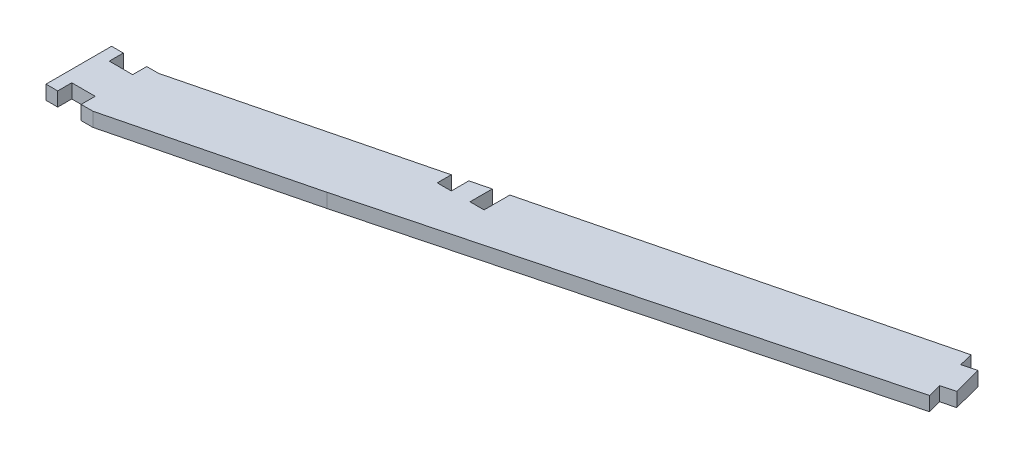
SolidWorks part; units mm, degrees
ref_plane "Front Plane" through (0, 0, 0) normal (0, 0, 1) x (1, 0, 0)
ref_plane "Top Plane" through (0, 0, 0) normal (0, 1, 0) x (1, 0, 0)
ref_plane "Right Plane" through (0, 0, 0) normal (1, 0, 0) x (0, 0, -1)
sketch "Sketch1" plane through (0, 0, 0) normal (0, 1, 0) x (1, 0, 0)
  line L0 (-450, 300) -> (-400, 300)
  line L1 (-400, 300) -> (-200, 250)
  line L2 (-200, 250) -> (200, 250) construction
  line L3 (200, 250) -> (600, 40) construction
  line L4 (600, 40) -> (1200, 40)
  line L5 (-450, -300) -> (-400, -300)
  line L6 (-400, -300) -> (-200, -250)
  line L7 (-200, -250) -> (200, -250) construction
  line L8 (200, -250) -> (600, -40) construction
  line L9 (600, -40) -> (1200, -40)
  line L10 (600, 40) -> (600, -40) construction
  line L11 (200, -250) -> (200, 250) construction
  line L12 (-200, 250) -> (-200, -250) construction
  line L13 (-400, -300) -> (-400, 300) construction
  line L14 (0, 0) -> (200, 0) construction
  line L15 (0, 250) -> (0, 0) construction
  line L16 (1200, 40) -> (1200, -40)
  line L17 (-450, 300) -> (-450, -300)
  line L18 (600, 0) -> (200, 0) construction
  line L19 (-450, 0) -> (-400, 0) construction
  line L20 (-400, 0) -> (-200, 0) construction
  line L21 (-200, 0) -> (0, 0) construction
  line L22 (-200, 250) -> (600, 40)
  line L23 (600, -40) -> (-200, -250)
  dimension "D1" = 600
  dimension "D2" = 200
  dimension "D3" = 50
  dimension "D4" = 400
  dimension "D5" = 500
  dimension "D6" = 80
  dimension "D7" = 600
  dimension "D8" = 400
extrude "Boss-Extrude1" add sketch "Sketch1" along normal blind 15
sketch "Sketch2" plane through (0, 0, 0) normal (0, 0, 1) x (1, 0, 0)
  line L0 (-450, 0) -> (-450, -40)
  line L1 (-450, -40) -> (-400, -40)
  line L2 (-400, -40) -> (-400, 0)
  line L3 (-400, 0) -> (-200, 0) construction
  line L4 (-400, 0) -> (-450, 0)
  line L5 (-440, -15) -> (-440, -40)
  line L6 (-410, -15) -> (-410, -40)
  line L7 (-425, 0) -> (-425, -15) construction
  circle A0 centre (-425, -15) radius 15
  dimension "D1" = 30
  dimension "D2" = 40
extrude "Boss-Extrude2" add sketch "Sketch2" along normal up to surface and the other way up to surface contours L4 L7 A0 L6 L1 L2 | L7 L4 L0 L1 L5 A0 up to face at (-425, 7.5, 300) other way up to face at (-425, 7.5, -300)
sketch "Sketch4" plane through (0, 0, 0) normal (0, 1, 0) x (1, 0, 0)
  line L0 (-450, 230) -> (-400, 230)
  line L1 (-450, 300) -> (-450, -300) construction
  line L2 (-400, 230) -> (-150, 167.5)
  line L3 (-150, 167.5) -> (-150, -167.5)
  line L4 (-150, -167.5) -> (-400, -230)
  line L5 (-400, -230) -> (-450, -230)
  line L6 (-400, 230) -> (-400, -230) construction
  line L7 (-200, 250) -> (-200, -250) construction
  line L9 (-200, 0) -> (-150, 0) construction
  line L10 (-400, -230) -> (-400, -300) construction
  line L11 (-400, -300) -> (-200, -250) construction
  line L12 (-450, 230) -> (-450, -230)
  line L14 (-200, 250) -> (-400, 300) construction
  line L15 (-100, 155) -> (-100, -155)
  line L16 (-100, -155) -> (520, 0)
  line L17 (520, 0) -> (-100, 155)
  line L18 (520, 0) -> (-100, 0) construction
  dimension "D1" = 460
  dimension "D2" = 300
  dimension "D3" = 50
extrude "Cut-Extrude2" cut sketch "Sketch4" against normal through all both and the other way through all
sketch "Sketch5" plane through (0, 0, 0) normal (1, 0, 0) x (0, 0, -1)
  line L0 (-300, 0) -> (-230, 0) construction
  line L1 (-285, 0) -> (-245, 0)
  line L2 (-285, 0) -> (-285, -40)
  line L3 (-285, -40) -> (-245, -40)
  line L4 (-245, 0) -> (-245, -40)
  line L5 (-300, -40) -> (-230, -40) construction
  line L6 (230, 0) -> (300, 0) construction
  line L7 (245, 0) -> (285, 0)
  line L8 (245, 0) -> (245, -40)
  line L9 (245, -40) -> (285, -40)
  line L10 (285, 0) -> (285, -40)
  line L11 (230, -40) -> (300, -40) construction
  line L12 (-300, 0) -> (-300, -40) construction
  line L13 (230, -40) -> (230, 0) construction
  line L14 (300, 0) -> (300, -40) construction
  dimension "D1" = 15
  dimension "D2" = 15
  dimension "D3" = 15
  dimension "D4" = 15
extrude "Cut-Extrude3" cut sketch "Sketch5" against normal through all
sketch "Sketch7" plane through (1200, 0, 0) normal (1, 0, 0) x (0, 0, -1)
  line L1 (-40, 15) -> (-87.5, 50)
  line L2 (-87.5, 50) -> (-87.5, 88.7)
  line L3 (-87.5, 88.7) -> (87.5, 88.7)
  line L4 (87.5, 88.7) -> (87.5, 50)
  line L5 (87.5, 50) -> (40, 15)
  line L7 (-40, 15) -> (40, 15)
  line L8 (-20, 50) -> (-20, 88.7)
  line L9 (87.5, 50) -> (-87.5, 50) construction
  line L10 (0, 88.7) -> (0, 50) construction
  line L11 (-20, 88.7) -> (20, 88.7)
  line L12 (0, 50) -> (0, 0) construction
  line L13 (20, 88.7) -> (20, 50)
  line L14 (-73, 88.7) -> (-63, 88.7)
  line L15 (-73, 88.7) -> (-73, 63.2)
  line L16 (-73, 63.2) -> (-63, 63.2)
  line L17 (-63, 88.7) -> (-63, 63.2)
  line L18 (48.5, 88.7) -> (58.5, 88.7)
  line L19 (48.5, 88.7) -> (48.5, 63.2)
  line L20 (48.5, 63.2) -> (58.5, 63.2)
  line L21 (58.5, 88.7) -> (58.5, 63.2)
  circle A0 centre (0, 50) radius 20
  dimension "D3" = 40
  dimension "D1" = 175
  dimension "D2" = 50
  dimension "D4" = 25.5
  dimension "D5" = 10
  dimension "D6" = 63
  dimension "D7" = 48.5
  dimension "D8" = 38.7
extrude "Boss-Extrude4" add sketch "Sketch7" against normal blind 75
sketch "Sketch8" plane through (0, 0, 0) normal (0, 0, 1) x (1, 0, 0)
  line L0 (1125, 88.7) -> (1200, 88.7) construction
  line L1 (1140, 88.7) -> (1185, 88.7)
  line L2 (1140, 88.7) -> (1140, 15)
  line L3 (1140, 15) -> (1185, 15)
  line L4 (1185, 88.7) -> (1185, 15)
  line L5 (1125, 15) -> (1200, 15) construction
  line L6 (1125, 50) -> (1125, 88.7) construction
  line L7 (1200, 50) -> (1200, 88.7) construction
  line L8 (1155, 88.7) -> (1170, 88.7) construction
  line L9 (1155, 88.7) -> (1170, 88.7)
  line L10 (1155, 88.7) -> (1155, 15)
  line L11 (1155, 15) -> (1170, 15)
  line L12 (1170, 88.7) -> (1170, 15)
  line L15 (1162.5, 50) -> (1162.5, 88.7) construction
  line L16 (1125, 50) -> (1200, 50) construction
  line L17 (1155, 88.7) -> (1170, 88.7) construction
  dimension "D1" = 15
  dimension "D2" = 15
  dimension "D3" = 15
extrude "Cut-Extrude4" cut sketch "Sketch8" against normal through all both and the other way through all contours L10 L1 L2 L3 | L1 L12 L3 L4
fillet "Fillet1" radius 5 53 edges at (1192.5, 50, 87.5) (1162.5, 50, 87.5) (1132.5, 50, 87.5) (1192.5, 50, -87.5) (1162.5, 50, -87.5) (1132.5, 50, -87.5) (1192.5, 88.7, -87.5) (1162.5, 88.7, -87.5) (1132.5, 88.7, -87.5) (1132.5, 88.7, -58.5) (1162.5, 88.7, -58.5) (1192.5, 88.7, -58.5) (1192.5, 88.7, -48.5) (1162.5, 88.7, -48.5) (1132.5, 88.7, -48.5) (1192.5, 88.7, -20) (1162.5, 88.7, -20) (1132.5, 88.7, -20) (1192.5, 88.7, 63) (1162.5, 88.7, 63) (1132.5, 88.7, 63) (1132.5, 88.7, 87.5) (1162.5, 88.7, 87.5) (1192.5, 88.7, 87.5) (1192.5, 88.7, 73) (1162.5, 88.7, 73) (1132.5, 88.7, 73) (1192.5, 88.7, 20) (1162.5, 88.7, 20) (1132.5, 88.7, 20) (600, 7.5, 40) (600, 7.5, -40) (520, 7.5, 0) (-440, -40, -292.5) (-440, -40, -237.5) (-400, -40, -292.5) (-400, -40, -237.5) (-450, -40, -237.5) (-410, -40, -237.5) (-450, -40, -292.5) (-410, -40, -292.5) (-150, 7.5, 167.5) (-100, 7.5, 155) (-150, 7.5, -167.5) (-100, 7.5, -155) (-450, -40, 237.5) (-410, -40, 237.5) (-440, -40, 237.5) (-400, -40, 237.5) (-450, -40, 292.5) (-440, -40, 292.5) (-400, -40, 292.5) (-410, -40, 292.5)
sketch "Sketch9" plane through (0, 0, 0) normal (0, 1, 0) x (1, 0, 0)
  line L35 (-450, -300) -> (-400, -300) construction
  line L36 (-425, -300) -> (-425, -285) construction
  line L37 (-450, 0) -> (0, 0) construction
  line L38 (-437.5, -300) -> (-412.5, -300)
  line L39 (-437.5, -300) -> (-437.5, -285)
  line L56 (1140, -40) -> (1140, -85.466) construction
  line L57 (1200, -40) -> (1185, -40)
  line L58 (1200, -40) -> (1200, -25)
  line L59 (1200, -25) -> (1185, -25)
  line L60 (1185, -40) -> (1185, -25)
  line L61 (1200, 40) -> (1185, 40)
  line L62 (1200, 40) -> (1200, 25)
  line L63 (1200, 25) -> (1185, 25)
  line L64 (1185, 40) -> (1185, 25)
  line L65 (1170, 40) -> (1155, 40)
  line L66 (1170, 40) -> (1170, 25)
  line L67 (1170, 25) -> (1155, 25)
  line L68 (1155, 40) -> (1155, 25)
  line L69 (1140, 40) -> (1125, 40)
  line L70 (1140, 40) -> (1140, 25)
  line L71 (1140, 25) -> (1125, 25)
  line L72 (1125, 40) -> (1125, 25)
  line L73 (1125, -40) -> (1140, -40)
  line L74 (1125, -40) -> (1125, -25)
  line L75 (1125, -25) -> (1140, -25)
  line L76 (1140, -40) -> (1140, -25)
  line L77 (1155, -40) -> (1170, -40)
  line L78 (1155, -40) -> (1155, -25)
  line L79 (1155, -25) -> (1170, -25)
  line L80 (1170, -40) -> (1170, -25)
  line L81 (600.6453, -40) -> (1200, -40) construction
  line L82 (1200, 40) -> (600.6453, 40) construction
  line L83 (1140, 40) -> (1125, 40) construction
  line L84 (1125, 85.466) -> (1125, 40) construction
  line L85 (1140, -25) -> (1155, -25) construction
  line L86 (1170, -25) -> (1185, -25) construction
  line L87 (1185, 25) -> (1170, 25) construction
  line L88 (1155, 25) -> (1140, 25) construction
  line L89 (-437.5, -285) -> (-412.5, -285)
  line L90 (-412.5, -300) -> (-412.5, -285)
  line L92 (-410, -230) -> (-440, -230) construction
  line L93 (-437.5, -230) -> (-412.5, -230)
  line L94 (-437.5, -230) -> (-437.5, -245)
  line L95 (-437.5, -245) -> (-412.5, -245)
  line L96 (-412.5, -230) -> (-412.5, -245)
  line L97 (-425, -245) -> (-400, -245) construction
  line L98 (-425, -285) -> (-425, -245) construction
  line L99 (-425, 285) -> (-425, 245) construction
  line L100 (-425, 300) -> (-425, 285) construction
  line L101 (-450, 300) -> (-400, 300) construction
  line L102 (-412.5, 230) -> (-412.5, 245)
  line L103 (-437.5, 245) -> (-412.5, 245)
  line L104 (-437.5, 230) -> (-437.5, 245)
  line L105 (-437.5, 230) -> (-412.5, 230)
  line L106 (-412.5, 300) -> (-412.5, 285)
  line L107 (-437.5, 285) -> (-412.5, 285)
  line L108 (-437.5, 300) -> (-437.5, 285)
  line L109 (-437.5, 300) -> (-412.5, 300)
  dimension "D1" = 15
  dimension "D2" = 25
  dimension "D3" = 15
extrude "Cut-Extrude5" cut sketch "Sketch9" against normal through all both and the other way through all
sketch "Sketch10" plane through (0, 0, 0) normal (0, 0, 1) x (1, 0, 0)
  line L1 (-450, 15) -> (1200, 15)
  line L2 (-450, 15) -> (-450, 0)
  line L3 (-450, 0) -> (1200, 0)
  line L4 (1200, 15) -> (1200, 0)
  line L5 (-450, 15) -> (-450, -35) construction
  line L6 (-486.0808, 110.0266) -> (1242.84, 110.0266)
  line L7 (-486.0808, 110.0266) -> (-486.0808, -68.8272)
  line L8 (-486.0808, -68.8272) -> (1242.84, -68.8272)
  line L9 (1242.84, 110.0266) -> (1242.84, -68.8272)
  dimension "D1" = 15
extrude "Cut-Extrude6" cut sketch "Sketch10" against normal through all both and the other way through all
sketch "Sketch11" plane through (0, 0, 0) normal (0, 1, 0) x (1, 0, 0)
  line L0 (-450, -315.625) -> (323.7848, -112.5065)
  line L1 (-200, -250) -> (599.3758, -40.1638) construction
  line L2 (-450, -315.625) -> (-450, -242.5)
  line L3 (-450, -230) -> (-450, -300) construction
  line L4 (-450, -242.5) -> (308.1542, -52.9615)
  line L5 (308.1542, -52.9615) -> (323.7848, -112.5065)
  line L6 (-400, -230) -> (-153.7873, -168.4468) construction
  line L7 (-450, -242.5) -> (-450, -230)
  line L8 (-450, -230) -> (-400, -230)
  line L9 (-150, -167.5) -> (-150, -182.5)
  line L10 (-150, -182.5) -> (-135, -182.5)
  line L11 (-135, -182.5) -> (-135, -163.75)
  line L12 (-100, -155) -> (-100, -182.5)
  line L13 (-100, -182.5) -> (-115, -182.5)
  line L14 (-115, -182.5) -> (-115, -158.75)
  line L15 (-100, 148.5961) -> (-100, -148.5961) construction
  line L16 (-150, -163.5961) -> (-150, 163.5961) construction
  line L17 (309.2763, -116.315) -> (305.4678, -101.8065)
  line L18 (-601.3695, -564.0724) -> (1251.3111, -564.0724)
  line L19 (-601.3695, -564.0724) -> (-601.3695, 511.8547)
  line L20 (-601.3695, 511.8547) -> (1251.3111, 511.8547)
  line L21 (1251.3111, -564.0724) -> (1251.3111, 511.8547)
  line L22 (305.4678, -101.8065) -> (319.9763, -97.998)
  line L23 (293.6011, -56.5997) -> (297.4095, -71.1082)
  line L24 (297.4095, -71.1082) -> (311.918, -67.2997)
  line L25 (305.4678, -101.8065) -> (297.4095, -71.1082) construction
  dimension "D1" = 800
  dimension "D2" = 15
  dimension "D3" = 15
  dimension "D4" = 15
  dimension "D5" = 15
extrude "Cut-Extrude9" cut sketch "Sketch11" against normal through all and the other way through all contours L18 L21 L20 L19 L7 L8 L4 L5 L0 L2 | L10 L11 L4 L9 | L14 L13 L12 L4 | L22 L17 L0 L5 | L23 L24 L5 L4
